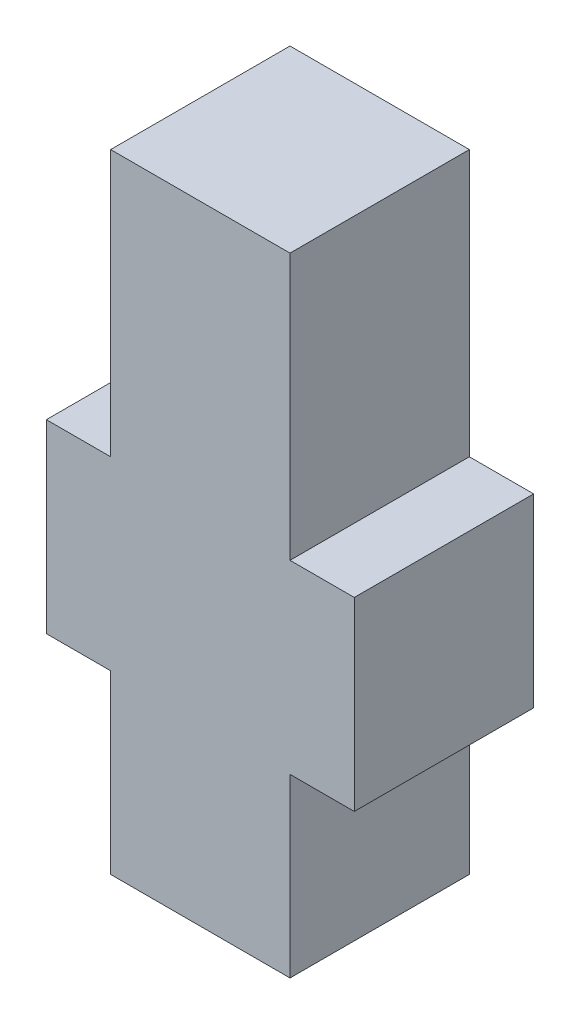
SolidWorks part; units mm, degrees
ref_plane "Спереди" through (0, 0, 0) normal (0, 0, 1) x (1, 0, 0)
ref_plane "Сверху" through (0, 0, 0) normal (0, 1, 0) x (1, 0, 0)
ref_plane "Справа" through (0, 0, 0) normal (1, 0, 0) x (0, 0, -1)
other "Configuration Table"
sketch "Канал_6" plane through (0, 0, 0) normal (0, 0, 1) x (1, 0, 0)
  line L0 (-3, -21) -> (3, -21)
  line L1 (3, -21) -> (3, 0)
  line L2 (3, 0) -> (-3, 0)
  line L3 (-3, 0) -> (-3, -21)
  line L4 (-3, -21) -> (3, 0) construction
  point P4 (0, -10.5)
  dimension "Ширина" = 6
  dimension "Глубина" = 21
  dimension "Положение_ОтКромки" = 10.5
extrude "Канал_сквозной" add sketch "Канал_6" along normal blind 6
sketch "Карман_гайки" plane through (0, 0, 0) normal (0, 0, 1) x (1, 0, 0)
  line L0 (-5.15, -15.1) -> (5.15, -15.1)
  line L1 (5.15, -15.1) -> (5.15, -8.9)
  line L2 (5.15, -8.9) -> (-5.15, -8.9)
  line L3 (-5.15, -8.9) -> (-5.15, -15.1)
  line L4 (-5.15, -15.1) -> (5.15, -8.9) construction
  point P4 (0, -12)
  dimension "Ширина" = 10.3
  dimension "Глубина" = 6.2
  dimension "Положение_ОтКромки" = 12
extrude "Гайка_10_3х6_2" add sketch "Карман_гайки" along normal blind 6
equation "\"D1@Гайка_10_3х6_2\"  = \"Толщина вертикальных стенок\""
equation "\"D1@Канал_сквозной\"  = \"Толщина вертикальных стенок\""
equation "\"Фанера\"=6"
equation "\"Ширина шипа\"=16"
equation "\"Межосевое шипов\"=40"
equation "\"Посадочный зазор\"=0.15"
equation "\"Основная фреза\"=6"
equation "\"Мелкая фреза\"=6"
equation "\"Запас разгрузки\"=0.05"
equation "\"Ширина образца\"=84"
equation "\"Высота образца\"=50"
equation "\"Канал М6\"=6"
equation "\"Гайка под ключ\"=10.3"
equation "\"Длина кармана гайки\"=6.2"
equation "\"Отступ гайки\"=12"
equation "\"Ширина@Канал_6\" = \"Канал М6\""
equation "\"Глубина@Канал_6\" = 21"
equation "\"Положение_ОтКромки@Канал_6\" =  -  (  - 10.5 ) "
equation "\"Ширина@Карман_гайки\" = \"Гайка под ключ\""
equation "\"Глубина@Карман_гайки\" = \"Длина кармана гайки\""
equation "\"Положение_ОтКромки@Карман_гайки\" =  -  (  - \"Отступ гайки\" ) "
equation "\"Ширина груза\"= 160"
equation "\"Глубина груза\"= 240"
equation "\"Высота груза\"= 160"
equation "\"Ширина ячейки\"= \"Ширина груза\" + 10"
equation "\"Глубина ячейки\"= \"Глубина груза\" + 10"
equation "\"Высота ячейки\"= \"Высота груза\" + 10 + 13"
equation "\"Колво ячеек ширина\"= 2"
equation "\"Колво ячеек высота\"= 2"
equation "\"Толщина стенки\" = \"Толщина тонких панелей\""
equation "\"Крепление дверцы\"= 5 "
equation "\"Ширина рейки\"= \"Толщина шестерни\""
equation "\"Высота рейки\"= 20"
equation "\"Высота пола\" = 2*\"Толщина тонких панелей\""
equation "\"Колво полозьев\"= 5"
equation "\"Отступ рейки\"= 20"
equation "\"Глубина каретки\"= \"Глубина ячейки\" + 30 + \"Мотор Y высота корпуса\" + 20"
equation "\"Длинна рейки\" = (\"Ширина ячейки\"+\"Толщина вертикальных стенок\"+\"Крепление дверцы\")*\"Колво ячеек ширина\"+\"Ширина ячейки выгрузки\"*\"Колво выгрузки\"+\"Толщина вертикальных стенок\"+2*\"Отступ крепления мотора фиксации\"-\"Крепление дверцы\"*\"Колво ячеек ширина\""
equation "\"Отступ шпильки\"= 26"
equation "\"Диаметр шпильки\"= 5"
equation "\"Длинна шпильки\" = (\"Высота ячейки\"+\"Толщина горизонтальных плит\"+\"Высота пола\")*\"Колво ячеек высота\"+2*(\"Толщина горизонтальных плит\"+\"Отступ рейки\")"
equation "\"Ширина пластины\"= 50  "
equation "\"Высота зона выгрузки\"= \"Высота ячейки\" * 2 + \"Толщина стенки\" * 2"
equation "\"Колво выгрузки\"= 1"
equation "\"Ширина ячейки выгрузки\" = \"Ширина ячейки\"+\"Толщина вертикальных стенок\"+2*\"Отступ крепления мотора фиксации\""
equation "\"Отступ крепления мотора фиксации\" = (\"Ширина пластины\"+20-\"Толщина вертикальных стенок\")/2"
equation "\"Мотор X ширина корпуса\"= 42.3"
equation "\"Мотор X высота корпуса\"= 42.3"
equation "\"Мотор X длина корпуса\"= 40"
equation "\"Мотор X вылет вала\"= 19.8"
equation "\"Мотор Y ширина корпуса\"= 42.3"
equation "\"Мотор Y высота корпуса\"= 42.3"
equation "\"Мотор Y длина корпуса\"= 48"
equation "\"Мотор Y вылет вала\"= 30"
equation "\"Мотор Z ширина корпуса\"= 42"
equation "\"Мотор Z высота корпуса\"= 42"
equation "\"Мотор Z длина корпуса\"= 40"
equation "\"Мотор Z вылет вала\"= 23"
equation "\"Мотор диаметр вала ПРЕДВ\"= 5"
equation "\"Мотор шаг крепления ПРЕДВ\"= 31"
equation "\"Мотор диаметр отверстий ПРЕДВ\"= 3"
equation "\"Мотор глубина отверстий ПРЕДВ\"= 4.5"
equation "\"Мотор диаметр буртика ПРЕДВ\"= 22"
equation "\"Мотор высота буртика ПРЕДВ\"= 2"
equation "\"Мотор диаметр шкива ПРЕДВ\"= 16"
equation "\"Мотор длина шкива ПРЕДВ\"= 12"
equation "\"Мотор отступ шкива ПРЕДВ\"= 5"
equation "\"Мотор X шаг градусов\"= 1.8"
equation "\"Мотор Y шаг градусов\"= 1.8"
equation "\"Мотор Z шаг градусов\"= 1.8"
equation "\"Мотор Y диаметр ротора\"= 25.78"
equation "\"Толщина шестерни\"= 10"
equation "\"Толщина тонких панелей\" = 6"
equation "\"Толщина вертикальных стенок\" = 6"
equation "\"Толщина горизонтальных плит\" = 6"
equation "\"Базовая высота корпуса\"= (\"Высота ячейки\"+\"Толщина тонких панелей\"+\"Высота пола\")*\"Колво ячеек высота\"+6*\"Толщина тонких панелей\"+\"Мотор X ширина корпуса\"+\"Мотор Y ширина корпуса\"+75"
equation "\"Высота корпуса\"= (\"Высота ячейки\"+\"Толщина горизонтальных плит\"+\"Высота пола\")*\"Колво ячеек высота\"+2*\"Толщина горизонтальных плит\"+4*\"Толщина тонких панелей\"+\"Мотор X ширина корпуса\"+\"Мотор Y ширина корпуса\"+75"
equation "\"Смещение центра корпуса\"= (\"Высота корпуса\"-\"Базовая высота корпуса\")/2-(\"Толщина горизонтальных плит\"-\"Толщина тонких панелей\")"
equation "\"Отметка пола\"= -\"Базовая высота корпуса\"/2+\"Толщина тонких панелей\""
equation "\"Отметка потолка\"= \"Отметка пола\"+\"Высота корпуса\"-2*\"Толщина горизонтальных плит\""
equation "\"Отметка верхней полки\"= \"Отметка потолка\"-(28+\"Толщина тонких панелей\")-\"Высота ячейки\"-\"Высота пола\""
equation "\"Отметка нижней полки\"= \"Отметка верхней полки\"-\"Высота ячейки\"-\"Высота пола\"-\"Толщина горизонтальных плит\""
